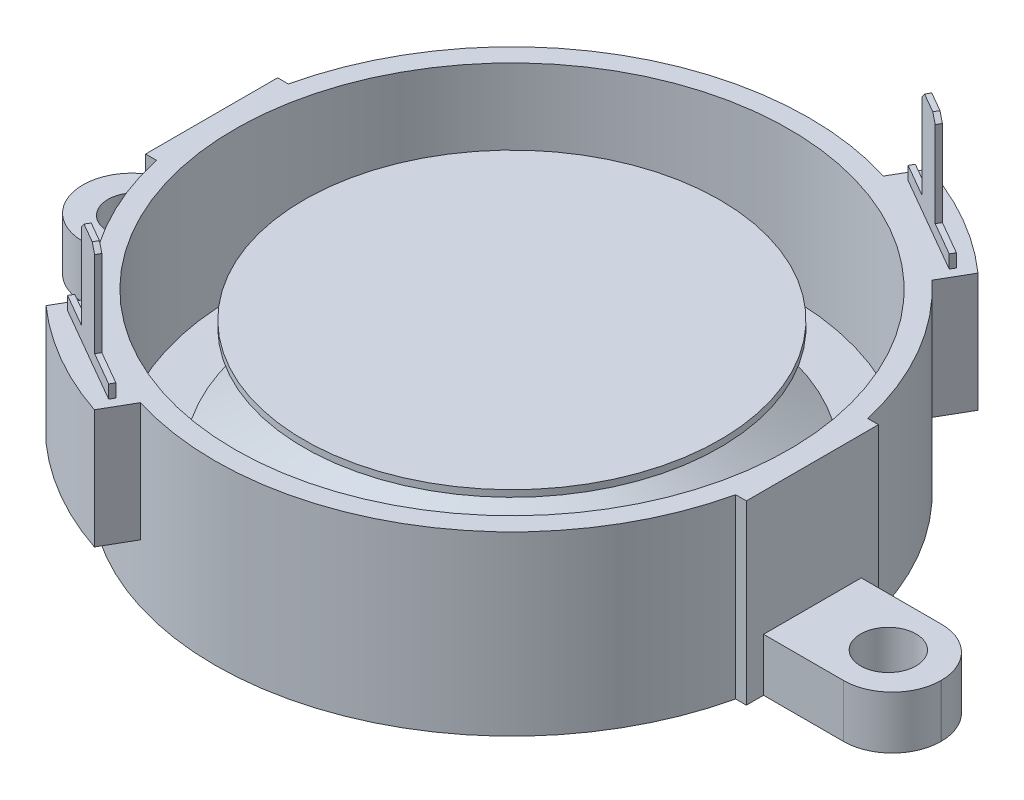
SolidWorks part; units mm, degrees
material "Полиамид ПА-6Б ТУ 6-05-988-87"
ref_plane "Спереди" through (0, 0, 0) normal (0, 0, 1) x (1, 0, 0)
ref_plane "Сверху" through (0, 0, 0) normal (0, 1, 0) x (1, 0, 0)
ref_plane "Справа" through (0, 0, 0) normal (1, 0, 0) x (0, 0, -1)
sketch "Эскиз1" plane through (0, 0, 0) normal (0, 1, 0) x (1, 0, 0)
  circle A0 centre (0, 0) radius 22.5
  dimension "D1" = 45
extrude "Бобышка-Вытянуть1" add sketch "Эскиз1" along normal blind 13.4
sketch "Эскиз2" plane through (0, 0, 0) normal (0, -1, 0) x (1, 0, 0)
  line L0 (0, 22.5) -> (0, 0) construction
  line L1 (22.1937, 3.7) -> (32.5, 3.7)
  line L3 (22.1937, -3.7) -> (32.5, -3.7)
  line L4 (32.5, 3.7) -> (32.5, -3.7)
  line L5 (-22.1937, -3.7) -> (-32.5, -3.7)
  line L7 (-22.1937, 3.7) -> (-32.5, 3.7)
  line L8 (-32.5, -3.7) -> (-32.5, 3.7)
  line L9 (32.5, 0) -> (-32.5, 0) construction
  circle A0 centre (0, 0) radius 22.5 construction
  circle A1 centre (0, 0) radius 22.5
  arc A2 (-22.1937, 3.7) -> (-22.1937, -3.7) centre (0, 0) ccw
  arc A3 (22.1937, -3.7) -> (22.1937, 3.7) centre (0, 0) ccw
  circle A4 centre (28.5, 0) radius 2.1
  circle A5 centre (-28.5, 0) radius 2.1
  dimension "D4" = 4.2
  dimension "D2" = 65
  dimension "D3" = 7.4
  dimension "D5" = 57
  dimension "D1" = 0
extrude "Бобышка-Вытянуть2" add sketch "Эскиз2" against normal blind 4
fillet "Скругление1" radius 3.69 4 edges at (32.5, 2, 3.7) (32.5, 2, -3.7) (-32.5, 2, -3.7) (-32.5, 2, 3.7)
sketch "Эскиз5" plane through (0, 13.4, 0) normal (0, 1, 0) x (1, 0, 0)
  circle A0 centre (0, 0) radius 21.0016
  dimension "D1" = 42.0032
extrude "Вырез-Вытянуть1" cut sketch "Эскиз5" against normal blind 11
sketch "Эскиз6" plane through (0, 0, 0) normal (0, -1, 0) x (-1, 0, 0)
  circle A0 centre (0, 0) radius 8
  dimension "D1" = 16
extrude "Вырез-Вытянуть2" cut sketch "Эскиз6" against normal blind 3
sketch "Эскиз8" plane through (0, 13.4, 0) normal (0, 1, 0) x (1, 0, 0)
  line L0 (7.9173, 23.7132) -> (6.6386, 21.4984)
  line L1 (0, 0) -> (13.8032, 23.9079) construction
  line L2 (16.5776, 18.7132) -> (15.2988, 16.4984)
  line L3 (0, 14.8355) -> (0, 0) construction
  line L4 (14.3383, 0) -> (0, 0) construction
  line L5 (-7.9173, -23.7132) -> (-6.6386, -21.4984)
  line L6 (-16.5776, -18.7132) -> (-15.2988, -16.4984)
  circle A0 centre (0, 0) radius 22.5 construction
  arc A1 (-15.2988, -16.4984) -> (-6.6386, -21.4984) centre (0, 0) ccw
  arc A2 (-16.5776, -18.7132) -> (-7.9173, -23.7132) centre (0, 0) ccw
  arc A3 (15.2988, 16.4984) -> (6.6386, 21.4984) centre (0, 0) ccw
  arc A4 (16.5776, 18.7132) -> (7.9173, 23.7132) centre (0, 0) ccw
  point P20 (0, 0)
  dimension "D1" = 50
  dimension "D2" = 10
  dimension "D3" = 30
  dimension "D4" = 2
extrude "Бобышка-Вытянуть6" add sketch "Эскиз8" against normal blind 9
sketch "Эскиз9" plane through (0, 13.4, 0) normal (0, 1, 0) x (1, 0, 0)
  line L0 (8.0694, 22.4766) -> (7.8694, 22.1302)
  line L1 (7.8694, 22.1302) -> (15.2306, 17.8802)
  line L2 (15.2306, 17.8802) -> (15.4306, 18.2266)
  line L3 (15.4306, 18.2266) -> (8.0694, 22.4766)
  line L4 (0, 0) -> (12.5, 21.6506) construction
  line L5 (7.9173, 23.7132) -> (6.6386, 21.4984) construction
  line L6 (0, 0) -> (11.2177, -6.4765) construction
  line L7 (-8.0694, -22.4766) -> (-15.4306, -18.2266)
  line L8 (-7.8694, -22.1302) -> (-8.0694, -22.4766)
  line L9 (-15.2306, -17.8802) -> (-7.8694, -22.1302)
  line L10 (-15.4306, -18.2266) -> (-15.2306, -17.8802)
  arc A0 (16.5776, 18.7132) -> (7.9173, 23.7132) centre (0, 0) ccw construction
  dimension "D1" = 8.5
  dimension "D2" = 0.4
  dimension "D3" = 47
extrude "Бобышка-Вытянуть7" add sketch "Эскиз9" along normal blind 1
sketch "Эскиз10" plane through (0, 14.4, 0) normal (0, 1, 0) x (1, 0, 0)
  line L0 (10.5809, 21.0266) -> (10.3809, 20.6802)
  line L1 (15.4306, 18.2266) -> (8.0694, 22.4766) construction
  line L2 (7.8694, 22.1302) -> (15.2306, 17.8802) construction
  line L3 (10.3809, 20.6802) -> (12.7191, 19.3302)
  line L4 (12.7191, 19.3302) -> (12.9191, 19.6766)
  line L5 (12.9191, 19.6766) -> (10.5809, 21.0266)
  line L6 (0, 0) -> (12.5, 21.6506) construction
  line L7 (0, 0) -> (11.9851, -6.9196) construction
  line L8 (-10.5809, -21.0266) -> (-12.9191, -19.6766)
  line L9 (-10.3809, -20.6802) -> (-10.5809, -21.0266)
  line L10 (-12.7191, -19.3302) -> (-10.3809, -20.6802)
  line L11 (-12.9191, -19.6766) -> (-12.7191, -19.3302)
  arc A0 (16.5776, 18.7132) -> (7.9173, 23.7132) centre (0, 0) ccw construction
  dimension "D1" = 2.7
extrude "Бобышка-Вытянуть8" add sketch "Эскиз10" along normal blind 7
chamfer "Фаска1" distance 0.5 angle 45 4 edges at (10.4809, 21.4, -20.8534) (12.8191, 21.4, -19.5034) (-12.8191, 21.4, 19.5034) (-10.4809, 21.4, 20.8534)
sketch "Эскиз11" plane through (0, 0, 0) normal (1, 0, 0) x (0, 0, -1)
  line L0 (-0.01, 0) -> (-0.01, 22.8012) construction
  line L1 (20.5, 2.4) -> (17.5, 2.4)
  line L2 (17.5, 2.4) -> (4.99, 9.6227)
  line L3 (4.99, 9.6227) -> (4.99, 10.9)
  line L4 (4.99, 10.9) -> (15.74, 10.9)
  line L5 (15.74, 10.9) -> (15.74, 11.4)
  line L6 (15.74, 11.4) -> (-0.01, 11.4)
  line L7 (8, 2.4) -> (-8, 2.4) construction
  line L8 (20.5, 2.4) -> (20.5, 1.9)
  line L9 (20.5, 1.9) -> (17.366, 1.9)
  line L10 (17.366, 1.9) -> (4.49, 9.334)
  line L11 (4.49, 9.334) -> (4.49, 10.9)
  line L12 (4.49, 10.9) -> (-0.01, 10.9)
  line L13 (-0.01, 10.9) -> (-0.01, 11.4)
  line L15 (16.4984, 13.4) -> (-22.5, 13.4) construction
  line L16 (22.5, 0) -> (22.5, 13.4) construction
  dimension "D1" = 0.5
  dimension "D2" = 0.5
  dimension "D3" = 3
  dimension "D4" = 2
  dimension "D5" = 0.5
  dimension "D6" = 0.5
  dimension "D7" = 2
  dimension "D8" = 150
  dimension "D9" = 5
  dimension "D10" = 31.5
revolve "Повернуть1" add sketch "Эскиз11" angle 360 about L0
sketch "Эскиз12" plane through (0, 4, 0) normal (0, 1, 0) x (1, 0, 0)
  circle A0 centre (0, 0) radius 22.5
  circle A1 centre (0, 0) radius 34
  arc A2 (6.6386, 21.4984) -> (-15.2988, -16.4984) centre (0, 0) ccw construction
  dimension "D1" = 68
extrude "Вырез-Вытянуть3" [suppressed] cut sketch "Эскиз12" against normal up to vertex up to point (-32.5, 0, 0.01)
sketch "Эскиз13" plane through (0, 0, 0) normal (0, -1, 0) x (1, 0, 0)
  circle A0 centre (0, 0) radius 9.5
  dimension "D1" = 19
extrude "Вырез-Вытянуть4" cut sketch "Эскиз13" against normal blind 2
sketch "Эскиз15" plane through (0, 0, 0) normal (0, -1, 0) x (1, 0, 0)
  line L0 (0, 0) -> (-13.2112, 0) construction
  line L1 (-21.9374, 5) -> (-22.75, 5)
  line L2 (-21.9374, -5) -> (-22.75, -5)
  line L3 (-22.75, 5) -> (-22.75, -5)
  line L4 (0, 0) -> (0, 11.1502) construction
  line L5 (22.75, 5) -> (22.75, -5)
  line L6 (21.9374, -5) -> (22.75, -5)
  line L7 (21.9374, 5) -> (22.75, 5)
  arc A0 (22.1937, 3.7) -> (-22.1937, 3.7) centre (0, 0) ccw construction
  arc A1 (-21.9374, -5) -> (-21.9374, 5) centre (0, 0) cw
  arc A2 (21.9374, -5) -> (21.9374, 5) centre (0, 0) ccw
  dimension "D2" = 45.5
  dimension "D1" = 10
extrude "Бобышка-Вытянуть10" add sketch "Эскиз15" against normal up to surface (13.4 mm away) up to face at (0, 13.4, 21.0016)
